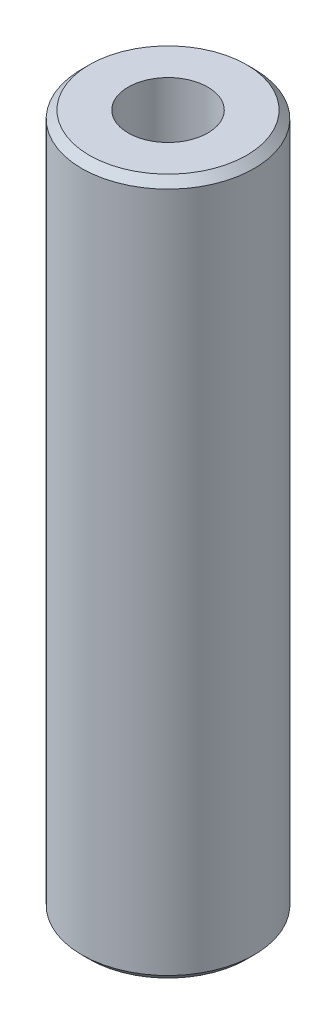
SolidWorks part; units mm, degrees
ref_plane "Front Plane" through (0, 0, 0) normal (0, 0, 1) x (1, 0, 0)
ref_plane "Top Plane" through (0, 0, 0) normal (0, 1, 0) x (1, 0, 0)
ref_plane "Right Plane" through (0, 0, 0) normal (1, 0, 0) x (0, 0, -1)
sketch "Sketch1" plane through (0, 0, 0) normal (0, 1, 0) x (1, 0, 0)
  circle A0 centre (0, 0) radius 15
  dimension "SHAFT_OD" = 30
extrude "Boss-Extrude1" add sketch "Sketch1" along normal blind 121.199
sketch "Sketch2" plane through (0, 0, 0) normal (0, 1, 0) x (1, 0, 0)
  circle A0 centre (0, 0) radius 6.9297
  dimension "BORE_D" = 13.8593
extrude "Cut-Extrude1" cut sketch "Sketch2" along normal through all
chamfer "Chamfer1" distance 1.3229 angle 45 2 edges at (0, 121.199, 15) (0, 0, 15)
